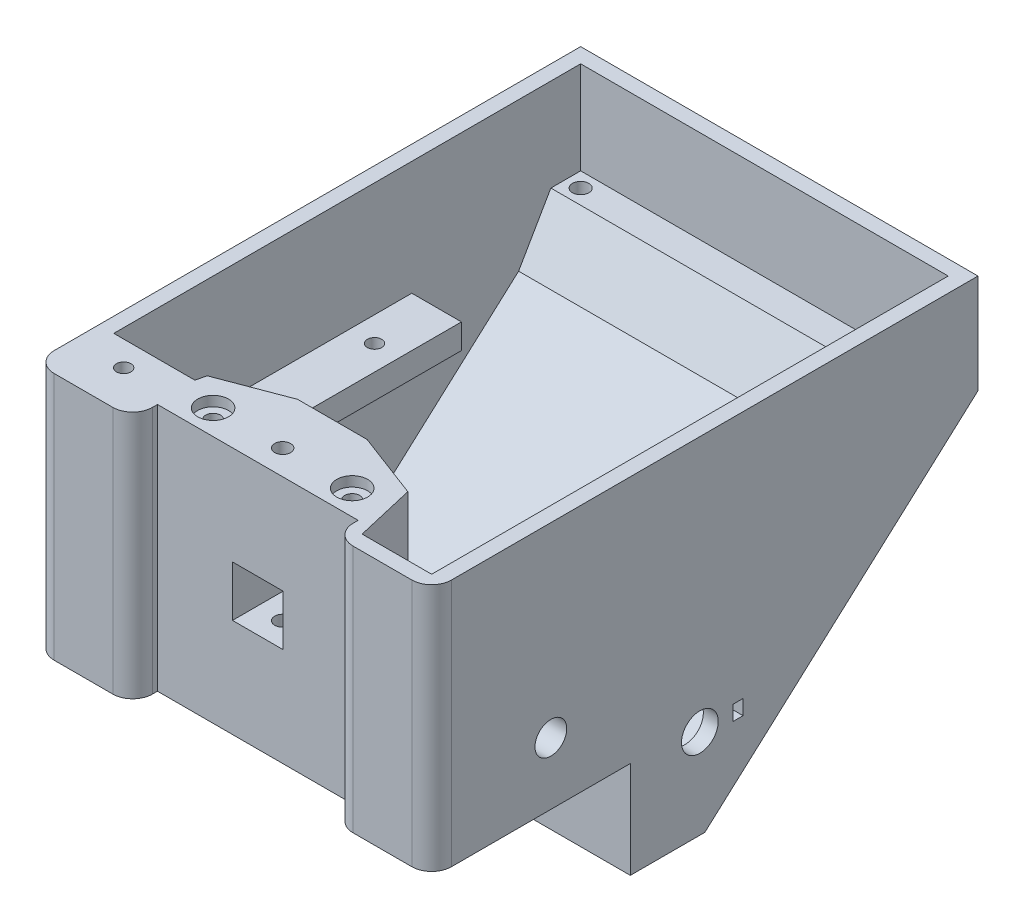
SolidWorks part; units mm, degrees
ref_plane "Спереди" through (0, 0, 0) normal (0, 0, 1) x (1, 0, 0)
ref_plane "Сверху" through (0, 0, 0) normal (0, 1, 0) x (1, 0, 0)
ref_plane "Справа" through (0, 0, 0) normal (1, 0, 0) x (0, 0, -1)
sketch "Sketch2" plane through (0, 0, 0) normal (1, 0, 0) x (0, 0, -1)
  line L0 (-27.3205, 20.9982) -> (-27.3205, -29.0018)
  line L1 (-27.3205, -29.0018) -> (12.6795, -29.0018)
  line L2 (12.6795, -29.0018) -> (12.6795, -48.5114)
  line L3 (12.6795, -48.5114) -> (27.6795, -48.5114)
  line L4 (82.6795, 20.9982) -> (82.6795, 0.9982)
  line L5 (82.6795, 20.9982) -> (-27.3205, 20.9982)
  line L6 (82.6795, 0.9982) -> (27.6795, -48.5114)
  dimension "D1" = 110
  dimension "D2" = 50
  dimension "D3" = 40
  dimension "D4" = 15
  dimension "D5" = 20
extrude "Boss-Extrude1" add sketch "Sketch2" along normal blind 80
shell "Shell1" thickness 3 removed face at (40, 20.9982, -27.6795)
sketch "Sketch3" plane through (0, 0, 24.3205) normal (0, 0, -1) x (-1, 0, 0)
  line L0 (-40, 20.9982) -> (-40, -26.0018) construction
  line L3 (-77, 20.9982) -> (-3, 20.9982) construction
  line L4 (-77, -26.0018) -> (-3, -26.0018) construction
  line L6 (-17, 20.9982) -> (-63, 20.9982)
  line L7 (-17, 20.9982) -> (-17, -26.0018)
  line L8 (-17, -26.0018) -> (-63, -26.0018)
  line L9 (-63, 20.9982) -> (-63, -26.0018)
  line L10 (-17, 20.9982) -> (-63, -26.0018) construction
  line L11 (-17, -26.0018) -> (-63, 20.9982) construction
  point P6 (-40, -2.5018)
  dimension "D1" = 46
extrude "Boss-Extrude2" add sketch "Sketch3" along normal blind 17
sketch "Sketch4" plane through (0, 0, 27.3205) normal (0, 0, 1) x (1, 0, 0)
  line L0 (0, 20.9982) -> (80, -29.0018) construction
  line L2 (45.1, -9.1018) -> (34.9, -9.1018)
  line L3 (45.1, -9.1018) -> (45.1, 1.0982)
  line L4 (45.1, 1.0982) -> (34.9, 1.0982)
  line L5 (34.9, -9.1018) -> (34.9, 1.0982)
  line L6 (45.1, -9.1018) -> (34.9, 1.0982) construction
  line L7 (45.1, 1.0982) -> (34.9, -9.1018) construction
  point P4 (40, -4.0018)
  dimension "D1" = 10.2
extrude "Cut-Extrude1" cut sketch "Sketch4" against normal up to surface (20 mm away) up to face at (40, -2.5018, 7.3205)
sketch "Sketch6" plane through (0, -29.0018, 0) normal (0, -1, 0) x (1, 0, 0)
  line L0 (40, 27.3205) -> (40, -12.6795) construction
  line L1 (47.5, -5.4795) -> (32.5, -5.4795) construction
  line L2 (47.5, -5.4795) -> (47.5, 7.3205) construction
  line L3 (47.5, 7.3205) -> (32.5, 7.3205) construction
  line L4 (32.5, -5.4795) -> (32.5, 7.3205) construction
  line L5 (47.5, -5.4795) -> (32.5, 7.3205) construction
  line L6 (47.5, 7.3205) -> (32.5, -5.4795) construction
  line L7 (80, -12.6795) -> (0, -12.6795) construction
  line L8 (51.5, 0.9205) -> (28.5, 0.9205) construction
  line L9 (80, 27.3205) -> (0, 27.3205) construction
  line L11 (36, -5.4795) -> (21, -5.4795)
  line L12 (36, -5.4795) -> (36, 7.3205)
  line L13 (36, 7.3205) -> (21, 7.3205)
  line L14 (21, -5.4795) -> (21, 7.3205)
  line L15 (36, -5.4795) -> (21, 7.3205) construction
  line L16 (36, 7.3205) -> (21, -5.4795) construction
  line L17 (44, -5.4795) -> (59, -5.4795)
  line L18 (44, -5.4795) -> (44, 7.3205)
  line L19 (44, 7.3205) -> (59, 7.3205)
  line L20 (59, -5.4795) -> (59, 7.3205)
  line L21 (44, -5.4795) -> (59, 7.3205) construction
  line L22 (44, 7.3205) -> (59, -5.4795) construction
  point P0 (40, 0.9205)
  point P14 (40, 0.9205)
  dimension "D1" = 15
  dimension "D2" = 12.8
  dimension "D3" = 8
  dimension "D4" = 20
extrude "Cut-Extrude2" cut sketch "Sketch6" against normal up to surface (3 mm away) up to face at (40, -26.0018, 10.0705)
sketch "Sketch7" plane through (0, 0, 27.3205) normal (0, 0, 1) x (1, 0, 0)
  line L0 (40, 20.9982) -> (40, -29.0018) construction
  line L1 (80, 20.9982) -> (0, 20.9982) construction
  line L2 (80, -29.0018) -> (0, -29.0018) construction
  line L4 (60.2, -29.0018) -> (19.8, -29.0018)
  line L5 (60.2, -29.0018) -> (60.2, 20.9982)
  line L6 (60.2, 20.9982) -> (19.8, 20.9982)
  line L7 (19.8, -29.0018) -> (19.8, 20.9982)
  line L8 (60.2, -29.0018) -> (19.8, 20.9982) construction
  line L9 (60.2, 20.9982) -> (19.8, -29.0018) construction
  point P6 (40, -4.0018)
  dimension "D1" = 40.4
extrude "Cut-Extrude3" cut sketch "Sketch7" against normal blind 5
fillet "Fillet1" radius 4 4 edges at (19.8, -4.0018, 27.3205) (60.2, -4.0018, 27.3205) (80, -4.0018, 27.3205) (0, -4.0018, 27.3205)
sketch "Sketch12" plane through (0, 20.9982, 0) normal (0, 1, 0) x (1, 0, 0)
  line L0 (19.8, -22.3205) -> (19.8, -12.3205) construction
  line L1 (19.8, -12.3205) -> (60.2, -12.3205) construction
  line L2 (60.2, -12.3205) -> (60.2, -22.3205) construction
  line L3 (33, -7.3205) -> (19.8, -12.3205)
  line L4 (17, -7.3205) -> (63, -7.3205) construction
  line L5 (19.8, -12.3205) -> (17, -24.3205)
  line L6 (17, -24.3205) -> (17, -7.3205)
  line L7 (17, -7.3205) -> (33, -7.3205)
  line L8 (47, -7.3205) -> (63, -7.3205)
  line L9 (63, -7.3205) -> (63, -24.3205)
  line L10 (63, -24.3205) -> (60.2, -12.3205)
  line L11 (60.2, -12.3205) -> (47, -7.3205)
  dimension "D1" = 10
  dimension "D2" = 16
extrude "Cut-Extrude7" cut sketch "Sketch12" against normal up to surface (47 mm away) up to face at (40, -26.0018, 5.4955)
sketch "Sketch13" plane through (0, 20.9982, 0) normal (0, 1, 0) x (1, 0, 0)
  line L0 (19.8, -22.3205) -> (19.8, -12.3205) construction
  line L1 (19.8, -12.3205) -> (60.2, -12.3205) construction
  line L2 (60.2, -12.3205) -> (60.2, -22.3205) construction
  line L3 (60.2, -17.3205) -> (19.8, -17.3205) construction
  circle A0 centre (26, -17.3205) radius 1.5
  circle A1 centre (54, -17.3205) radius 1.5
  point P14 (40, -17.3205)
  dimension "D1" = 3
  dimension "D2" = 28
  dimension "D3" = 14
  dimension "D4" = 6.2
extrude "Cut-Extrude8" cut sketch "Sketch13" against normal blind 25
sketch "Sketch14" plane through (0, 20.9982, 0) normal (0, 1, 0) x (1, 0, 0)
  circle A0 centre (26, -17.3205) radius 3.1
  circle A1 centre (54, -17.3205) radius 3.1
  dimension "D1" = 6.2
extrude "Cut-Extrude9" cut sketch "Sketch14" against normal blind 2
sketch "Sketch17" plane through (77, 0, 0) normal (-1, 0, 0) x (0, 0, 1)
  line L0 (-45.6795, -2.0018) -> (-0.6795, -2.0018)
  line L1 (-0.6795, -2.0018) -> (-0.6795, -7.0018)
  line L2 (-0.6795, -7.0018) -> (-45.6795, -7.0018)
  line L3 (-45.6795, -7.0018) -> (-45.6795, -2.0018)
  line L4 (-79.6795, 20.9982) -> (24.3205, 20.9982) construction
  line L5 (-79.6795, 2.3342) -> (-79.6795, 20.9982) construction
  dimension "D1" = 45
  dimension "D2" = 5
  dimension "D3" = 23
  dimension "D4" = 34
extrude "Boss-Extrude5" add sketch "Sketch17" along normal up to surface (74 mm away) up to face at (3, -14.0994, -24.0865)
sketch "Sketch18" plane through (0, -2.0018, 0) normal (0, 1, 0) x (1, 0, 0)
  line L0 (40, 0.6795) -> (40, 45.6795) construction
  line L1 (3, 0.6795) -> (77, 0.6795) construction
  line L2 (3, 45.6795) -> (77, 45.6795) construction
  line L3 (77, 0.6795) -> (77, 45.6795) construction
  line L4 (13, 0.6795) -> (67, 0.6795)
  line L5 (13, 0.6795) -> (13, 45.6795)
  line L6 (13, 45.6795) -> (67, 45.6795)
  line L7 (67, 0.6795) -> (67, 45.6795)
  line L8 (13, 0.6795) -> (67, 45.6795) construction
  line L9 (13, 45.6795) -> (67, 0.6795) construction
  point P6 (40, 23.1795)
  dimension "D1" = 10
extrude "Cut-Extrude10" cut sketch "Sketch18" against normal up to next
sketch "Sketch19" plane through (0, -2.0018, 0) normal (0, 1, 0) x (1, 0, 0)
  line L0 (72, 45.6795) -> (72, 0.6795) construction
  line L1 (67, 45.6795) -> (77, 45.6795) construction
  line L2 (67, 0.6795) -> (77, 0.6795) construction
  line L3 (8, 45.6795) -> (8, 0.6795) construction
  line L4 (3, 45.6795) -> (13, 45.6795) construction
  line L5 (3, 0.6795) -> (13, 0.6795) construction
  circle A0 centre (72, 37.1795) radius 1.45
  circle A1 centre (72, 6.1795) radius 1.45
  circle A2 centre (8, 33.1795) radius 1.45
  circle A3 centre (8, 6.1795) radius 1.45
  point P20 (72, 23.1795)
  point P21 (8, 23.1795)
  dimension "D1" = 2.9
  dimension "D2" = 14
  dimension "D3" = 17
  dimension "D4" = 17
  dimension "D5" = 10
extrude "Cut-Extrude11" cut sketch "Sketch19" against normal up to next
sketch "Sketch21" plane through (0, -26.0018, 0) normal (0, 1, 0) x (1, 0, 0)
  line L0 (3, -24.3205) -> (3, -14.3205)
  line L1 (3, -24.3205) -> (3, 15.6795) construction
  line L2 (3, -14.3205) -> (19.3333, -14.3205)
  line L3 (19.8, -12.3205) -> (17, -24.3205) construction
  line L4 (19.3333, -14.3205) -> (17, -24.3205)
  line L6 (3, -24.3205) -> (17, -24.3205)
  dimension "D1" = 10
extrude "Boss-Extrude6" add sketch "Sketch21" along normal up to surface (47 mm away) up to face at (54, 20.9982, 20.4205)
sketch "Sketch22" plane through (0, 20.9982, 0) normal (0, 1, 0) x (1, 0, 0)
  line L0 (0, 82.6795) -> (0, -23.3205) construction
  line L1 (15.8, -27.3205) -> (4, -27.3205) construction
  circle A0 centre (10, -19.3205) radius 1.45
  dimension "D1" = 2.9
  dimension "D2" = 10
  dimension "D3" = 8
extrude "Cut-Extrude12" cut sketch "Sketch22" against normal through all
sketch "Sketch24" plane through (80, 0, 0) normal (1, 0, 0) x (0, 0, -1)
  line L0 (12.6795, -48.5114) -> (27.6795, -48.5114) construction
  line L1 (12.6795, -29.0018) -> (12.6795, -48.5114) construction
  line L2 (18.1795, -30.5114) -> (18.1795, -19.0114) construction
  line L3 (18.1795, -19.0114) -> (35.1795, -19.0114) construction
  line L4 (35.1795, -19.0114) -> (35.1795, -30.5114) construction
  line L5 (26.6795, -19.0114) -> (26.6795, -39.0114) construction
  line L6 (30.3795, -30.5114) -> (34.3795, -30.5114) construction
  line L8 (33.3795, -32.0114) -> (35.3795, -32.0114)
  line L9 (33.3795, -32.0114) -> (33.3795, -29.0114)
  line L10 (33.3795, -29.0114) -> (35.3795, -29.0114)
  line L11 (35.3795, -32.0114) -> (35.3795, -29.0114)
  line L12 (33.3795, -32.0114) -> (35.3795, -29.0114) construction
  line L13 (33.3795, -29.0114) -> (35.3795, -32.0114) construction
  circle A0 centre (26.6795, -30.5114) radius 3.7
  circle A1 centre (26.6795, -30.5114) radius 8.5 construction
  dimension "D1" = 7.4
  dimension "D2" = 17
  dimension "D3" = 18
  dimension "D4" = 14
  dimension "D5" = 20
  dimension "D6" = 4
  dimension "D7" = 2
  dimension "D8" = 3
extrude "Cut-Extrude13" cut sketch "Sketch24" against normal up to next
sketch "Sketch26" plane through (3, 0, 0) normal (1, 0, 0) x (0, 0, -1)
  line L0 (79.6795, 2.3342) -> (63.6795, 2.3342)
  line L1 (63.6795, 2.3342) -> (63.6795, -12.0686)
  line L2 (26.5281, -45.5114) -> (79.6795, 2.3342) construction
  line L3 (63.6795, -12.0686) -> (79.6795, 2.3342)
  dimension "D1" = 16
extrude "Boss-Extrude7" add sketch "Sketch26" along normal up to surface (74 mm away) up to face at (77, -30.5114, -34.3795)
sketch "Sketch27" plane through (0, 2.3342, 0) normal (0, 1, 0) x (1, 0, 0)
  line L0 (3, 76.6795) -> (77, 76.6795) construction
  line L1 (3, 79.6795) -> (3, 63.6795) construction
  line L2 (77, 79.6795) -> (77, 63.6795) construction
  line L3 (80, 82.6795) -> (0, 82.6795) construction
  circle A0 centre (6, 76.6795) radius 1.65
  circle A1 centre (74, 76.6795) radius 1.65
  point P10 (40, 76.6795)
  dimension "D1" = 3.3
  dimension "D2" = 68
  dimension "D3" = 34
  dimension "D4" = 6
extrude "Cut-Extrude14" cut sketch "Sketch27" against normal blind 10
sketch "Sketch28" plane through (0, 2.3342, 0) normal (0, 1, 0) x (1, 0, 0)
  line L1 (74, 79.9295) -> (71.1854, 78.3045)
  line L2 (71.1854, 78.3045) -> (71.1854, 75.0545)
  line L3 (71.1854, 75.0545) -> (74, 73.4295)
  line L4 (74, 73.4295) -> (76.8146, 75.0545)
  line L5 (76.8146, 75.0545) -> (76.8146, 78.3045)
  line L6 (76.8146, 78.3045) -> (74, 79.9295)
  line L7 (6, 73.4295) -> (8.8146, 75.0545)
  line L8 (8.8146, 75.0545) -> (8.8146, 78.3045)
  line L9 (8.8146, 78.3045) -> (6, 79.9295)
  line L10 (6, 79.9295) -> (3.1854, 78.3045)
  line L11 (3.1854, 78.3045) -> (3.1854, 75.0545)
  line L12 (3.1854, 75.0545) -> (6, 73.4295)
  circle A0 centre (74, 76.6795) radius 3.25 construction
  circle A1 centre (6, 76.6795) radius 3.25 construction
  dimension "D1" = 6.5
extrude "Cut-Extrude15" cut sketch "Sketch28" against normal blind 32 from offset 3 offset against normal yes
sketch "Sketch29" plane through (0, -29.0018, 0) normal (0, -1, 0) x (1, 0, 0)
  line L0 (0, 23.3205) -> (0, -12.6795) construction
  line L1 (7.1854, 17.6955) -> (10, 16.0705)
  line L2 (10, 16.0705) -> (12.8146, 17.6955)
  line L3 (12.8146, 17.6955) -> (12.8146, 20.9455)
  line L4 (12.8146, 20.9455) -> (10, 22.5705)
  line L5 (10, 22.5705) -> (7.1854, 20.9455)
  line L6 (7.1854, 20.9455) -> (7.1854, 17.6955)
  circle A0 centre (10, 19.3205) radius 3.25 construction
  dimension "D1" = 6.5
extrude "Cut-Extrude16" cut sketch "Sketch29" against normal blind 30
sketch "Sketch30" plane through (0, -26.0018, 0) normal (0, 1, 0) x (1, 0, 0)
  line L0 (77, -24.3205) -> (63, -24.3205)
  line L1 (63, -24.3205) -> (60.2, -12.3205)
  line L2 (63, -24.3205) -> (60.2, -12.3205) construction
  line L3 (60.2, -12.3205) -> (77, -12.3205)
  line L4 (77, -24.3205) -> (77, 15.6795) construction
  line L5 (77, -12.3205) -> (77, -24.3205)
  dimension "D1" = 12
extrude "Boss-Extrude8" add sketch "Sketch30" along normal blind 20
sketch "Sketch31" plane through (0, -6.0018, 0) normal (0, 1, 0) x (1, 0, 0)
  line L0 (76, -27.3205) -> (64.2, -27.3205) construction
  line L1 (80, -23.3205) -> (80, 12.6795) construction
  circle A0 centre (72, -21.3205) radius 1.5
  dimension "D3" = 3
  dimension "D1" = 6
  dimension "D2" = 8
extrude "Cut-Extrude17" cut sketch "Sketch31" against normal through all
sketch "Sketch32" plane through (0, -29.0018, 0) normal (0, -1, 0) x (1, 0, 0)
  line L1 (72, 24.5705) -> (69.1854, 22.9455)
  line L2 (69.1854, 22.9455) -> (69.1854, 19.6955)
  line L3 (69.1854, 19.6955) -> (72, 18.0705)
  line L4 (72, 18.0705) -> (74.8146, 19.6955)
  line L5 (74.8146, 19.6955) -> (74.8146, 22.9455)
  line L6 (74.8146, 22.9455) -> (72, 24.5705)
  circle A0 centre (72, 21.3205) radius 3.25 construction
  dimension "D1" = 6.5
extrude "Cut-Extrude18" cut sketch "Sketch32" against normal blind 15
sketch "Sketch33" plane through (0, -2.0018, 0) normal (0, 1, 0) x (1, 0, 0)
  line L0 (67, 40.6795) -> (77, 40.6795)
  line L1 (67, 0.6795) -> (67, 45.6795) construction
  line L2 (77, 0.6795) -> (77, 45.6795) construction
  line L3 (77, 40.6795) -> (77, 45.6795)
  line L4 (77, 45.6795) -> (67, 45.6795)
  line L5 (67, 45.6795) -> (67, 40.6795)
  dimension "D1" = 5
extrude "Cut-Extrude19" cut sketch "Sketch33" against normal up to next
sketch "Sketch34" plane through (0, 20.9982, 0) normal (0, 1, 0) x (1, 0, 0)
  line L0 (54, -17.3205) -> (26, -17.3205) construction
  circle A0 centre (40, -17.3205) radius 1.6
  dimension "D1" = 3.2
extrude "Cut-Extrude20" cut sketch "Sketch34" against normal through all
sketch "Sketch36" plane through (0, -29.0018, 0) normal (0, -1, 0) x (1, 0, 0)
  line L1 (38.375, 20.1351) -> (36.75, 17.3205)
  line L2 (36.75, 17.3205) -> (38.375, 14.5059)
  line L3 (38.375, 14.5059) -> (41.625, 14.5059)
  line L4 (41.625, 14.5059) -> (43.25, 17.3205)
  line L5 (43.25, 17.3205) -> (41.625, 20.1351)
  line L6 (41.625, 20.1351) -> (38.375, 20.1351)
  circle A0 centre (40, 17.3205) radius 3.25 construction
  dimension "D1" = 6.5
extrude "Cut-Extrude22" cut sketch "Sketch36" against normal blind 14
sketch "Sketch37" plane through (80, 0, 0) normal (1, 0, 0) x (0, 0, -1)
  line L0 (-23.3205, -16.5114) -> (63.2281, -16.5114) construction
  line L1 (-23.3205, 20.9982) -> (-23.3205, -29.0018) construction
  line L2 (27.6795, -48.5114) -> (82.6795, 0.9982) construction
  line L3 (30.3795, -30.5114) -> (22.9795, -30.5114) construction
  circle A0 centre (-3.3205, -16.5114) radius 3.2
  circle A1 centre (26.6795, -30.5114) radius 3.7 construction
  point P14 (26.6795, -30.5114)
  dimension "D1" = 6.4
  dimension "D2" = 14
  dimension "D3" = 20
extrude "Cut-Extrude23" cut sketch "Sketch37" against normal up to next
sketch "Sketch38" plane through (77, 0, 0) normal (-1, 0, 0) x (0, 0, 1)
  line L0 (12.3205, -26.0018) -> (-15.6795, -26.0018) construction
  line L1 (8.3205, -7.021) -> (-1.6795, -7.021)
  line L2 (8.3205, -7.021) -> (8.3205, -26.0018)
  line L3 (8.3205, -26.0018) -> (-1.6795, -26.0018)
  line L4 (-1.6795, -7.021) -> (-1.6795, -26.0018)
  line L5 (8.3205, -7.021) -> (-1.6795, -26.0018) construction
  line L6 (8.3205, -26.0018) -> (-1.6795, -7.021) construction
  circle A0 centre (3.3205, -16.5114) radius 3.2
  point P0 (3.3205, -16.5114)
  dimension "D1" = 10
extrude "Boss-Extrude9" add sketch "Sketch38" along normal blind 3
sketch "Sketch40" plane through (3, 0, 0) normal (1, 0, 0) x (0, 0, -1)
  line L0 (18.1795, -30.5114) -> (18.1795, -19.0114) construction
  line L1 (18.1795, -19.0114) -> (35.1795, -19.0114) construction
  line L2 (35.1795, -19.0114) -> (35.1795, -30.5114) construction
  line L3 (26.6795, -19.0114) -> (26.6795, -39.0114) construction
  line L4 (30.3795, -30.5114) -> (34.3795, -30.5114) construction
  line L5 (33.3795, -32.0114) -> (35.3795, -32.0114) construction
  line L6 (33.3795, -32.0114) -> (33.3795, -29.0114) construction
  line L7 (33.3795, -29.0114) -> (35.3795, -29.0114) construction
  line L8 (35.3795, -32.0114) -> (35.3795, -29.0114) construction
  line L9 (33.3795, -32.0114) -> (35.3795, -29.0114) construction
  line L10 (33.3795, -29.0114) -> (35.3795, -32.0114) construction
  line L13 (22.9795, -30.5114) -> (18.9795, -30.5114) construction
  line L14 (12.6795, -29.0018) -> (12.6795, -48.5114) construction
  line L15 (17.9795, -29.0114) -> (19.9795, -29.0114)
  line L16 (17.9795, -29.0114) -> (17.9795, -32.0114)
  line L17 (17.9795, -32.0114) -> (19.9795, -32.0114)
  line L18 (19.9795, -29.0114) -> (19.9795, -32.0114)
  line L19 (17.9795, -29.0114) -> (19.9795, -32.0114) construction
  line L20 (17.9795, -32.0114) -> (19.9795, -29.0114) construction
  line L21 (12.6795, -48.5114) -> (27.6795, -48.5114) construction
  circle A0 centre (26.6795, -30.5114) radius 3.7
  circle A1 centre (26.6795, -30.5114) radius 8.5 construction
  dimension "D4" = 17
  dimension "D5" = 17
  dimension "D11" = 7.4
  dimension "D1" = 3
  dimension "D2" = 2
  dimension "D3" = 4
  dimension "D6" = 2
  dimension "D7" = 3
  dimension "D8" = 4
  dimension "D9" = 14
  dimension "D10" = 18
extrude "Cut-Extrude24" cut sketch "Sketch40" against normal up to next
chamfer "Chamfer1" distance 10 angle 60 1 edges at (40, 2.3342, -63.6795) first distance on face at (74, 2.3342, -75.0295)
sketch "Sketch41" plane through (0, -26.0018, 0) normal (0, 1, 0) x (1, 0, 0)
  line L0 (21, -0.9205) -> (3, -0.9205) construction
  line L1 (21, -7.3205) -> (21, 5.4795) construction
  line L2 (3, -14.3205) -> (3, 15.6795) construction
  line L4 (15.25, -4.1705) -> (8.75, -4.1705)
  line L5 (15.25, -4.1705) -> (15.25, 2.3295)
  line L6 (15.25, 2.3295) -> (8.75, 2.3295)
  line L7 (8.75, -4.1705) -> (8.75, 2.3295)
  line L8 (15.25, -4.1705) -> (8.75, 2.3295) construction
  line L9 (15.25, 2.3295) -> (8.75, -4.1705) construction
  point P6 (12, -0.9205)
  dimension "D1" = 6.5
extrude "Cut-Extrude25" cut sketch "Sketch41" against normal blind 1
sketch "Sketch42" plane through (0, -27.0018, 0) normal (0, 1, 0) x (1, 0, 0)
  line L0 (8.75, -0.9205) -> (15.25, -0.9205) construction
  line L1 (8.75, 2.3295) -> (8.75, -4.1705) construction
  line L2 (15.25, -4.1705) -> (15.25, 2.3295) construction
  circle A0 centre (12, -0.9205) radius 2.25
  dimension "D1" = 4.5
extrude "Cut-Extrude26" cut sketch "Sketch42" against normal through all
sketch "Sketch43" plane through (0, -29.0018, 0) normal (0, -1, 0) x (1, 0, 0)
  circle A0 centre (12, 0.9205) radius 4
  circle A1 centre (12, 0.9205) radius 2.25
  circle A2 centre (12, 0.9205) radius 2.25 construction
  dimension "D1" = 8
extrude "Boss-Extrude10" add sketch "Sketch43" along normal blind 2
fillet "Fillet2" radius 2 1 edges at (12, -29.0018, 4.9205)
fillet "Fillet3" radius 1 1 edges at (12, -31.0018, -3.0795)
sketch "Sketch44" plane through (0, -26.0018, 0) normal (0, 1, 0) x (1, 0, 0)
  line L1 (15.25, -4.1705) -> (8.75, -4.1705)
  line L2 (15.25, -4.1705) -> (15.25, 2.3295)
  line L3 (15.25, 2.3295) -> (8.75, 2.3295)
  line L4 (8.75, -4.1705) -> (8.75, 2.3295)
  line L5 (15.25, -4.1705) -> (8.75, 2.3295) construction
  line L6 (15.25, 2.3295) -> (8.75, -4.1705) construction
  line L7 (16.5, -5.4205) -> (7.5, -5.4205)
  line L8 (16.5, -5.4205) -> (16.5, 3.5795)
  line L9 (16.5, 3.5795) -> (7.5, 3.5795)
  line L10 (7.5, -5.4205) -> (7.5, 3.5795)
  line L11 (16.5, -5.4205) -> (7.5, 3.5795) construction
  line L12 (16.5, 3.5795) -> (7.5, -5.4205) construction
  point P0 (12, -0.9205)
  point P7 (12, -0.9205)
  dimension "D1" = 9
extrude "Boss-Extrude11" add sketch "Sketch44" along normal blind 2
